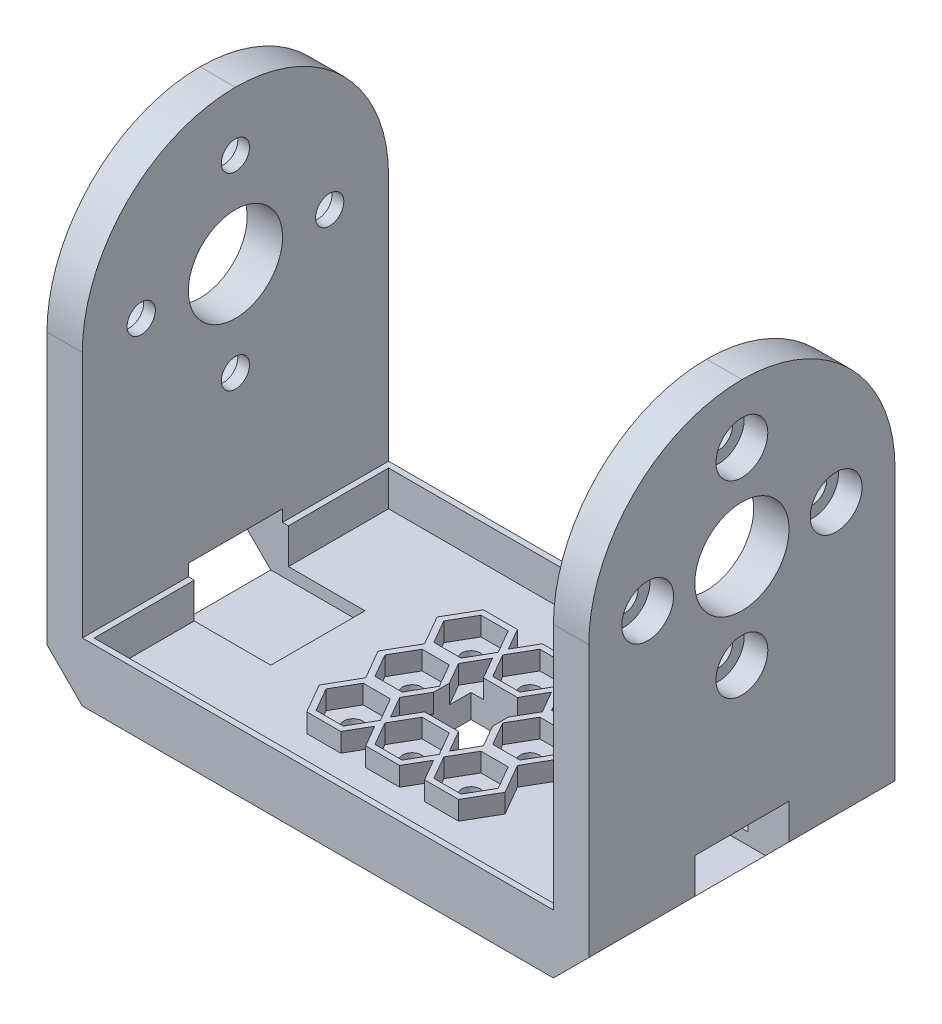
SolidWorks part; units mm, degrees
ref_plane "Front" through (0, 0, 0) normal (0, 0, 1) x (1, 0, 0)
ref_plane "Top" through (0, 0, 0) normal (0, 1, 0) x (1, 0, 0)
ref_plane "Right" through (0, 0, 0) normal (1, 0, 0) x (0, 0, -1)
sketch "草图1" plane through (0, 0, 0) normal (0, 1, 0) x (1, 0, 0)
  line L1 (-23, 13) -> (23, 13)
  line L2 (-23, 13) -> (-23, -13)
  line L3 (-23, -13) -> (23, -13)
  line L4 (23, 13) -> (23, -13)
  line L5 (-23, 13) -> (23, -13) construction
  line L6 (-23, -13) -> (23, 13) construction
  point P0 (0, 0)
  dimension "D1" = 46
  dimension "D2" = 26
extrude "凸台-拉伸1" add sketch "草图1" along normal blind 5
sketch "草图2" plane through (0, 5, 0) normal (0, 1, 0) x (1, 0, 0)
  line L0 (-23, -13) -> (23, -13) construction
  line L1 (-23, 13) -> (-20, 13)
  line L2 (-23, 13) -> (-23, -13)
  line L3 (-23, -13) -> (-20, -13)
  line L4 (-20, 13) -> (-20, -13)
  line L6 (23, 13) -> (20, 13)
  line L7 (23, 13) -> (23, -13)
  line L8 (23, -13) -> (20, -13)
  line L9 (20, 13) -> (20, -13)
  dimension "D1" = 3
  dimension "D2" = 3
extrude "凸台-拉伸2" add sketch "草图2" along normal blind 34
fillet "圆角1" radius 13 4 edges at (21.5, 39, -13) (-21.5, 39, -13) (21.5, 39, 13) (-21.5, 39, 13)
sketch "草图3" plane through (-23, 0, 0) normal (-1, 0, 0) x (0, 0, 1)
  line L0 (-13, 26) -> (13, 26) construction
  circle A0 centre (0, 26) radius 4
extrude "切除-拉伸1" cut sketch "草图3" against normal up to next
sketch "草图4" plane through (-23, 0, 0) normal (-1, 0, 0) x (0, 0, 1)
  line L0 (-13, 26) -> (13, 26) construction
  line L1 (0, 39) -> (0, 15.0372) construction
  point P9 (-8, 26)
  point P10 (0, 34)
  point P11 (8, 26)
  point P12 (0, 18)
  dimension "D1" = 8
  dimension "D2" = 8
  dimension "D3" = 8
  dimension "D4" = 8
hole_wizard "M2 凹头盖螺钉的柱形沉头孔1" positions "3D草图1" profile "草图5" counterbore size "M2" standard "ANSI Metric" end condition through all
sketch3d "3D草图1"
  point P0 (-23, 26, -8)
  point P3 (-23, 34, 0)
  point P6 (-23, 26, 8)
  point P9 (-23, 18, 0)
sketch "草图5" plane through (-23, 26, -8) normal (0, 1, 0) x (0, 0, 1)
  line L0 (0, 0) -> (0, 46)
  line L1 (0, 46) -> (1.2, 46)
  line L3 (1.2, 46) -> (1.2, 2)
  line L4 (1.2, 2) -> (2.2, 2)
  line L5 (2.2, 2) -> (2.2, 0)
  line L7 (2.2, 0) -> (0, 0)
  line L11 (0, -6.35) -> (0, 107.95) construction
  dimension "通孔孔直径" = 2.4
  dimension "通孔孔深度" = 46
  dimension "柱形沉头孔直径" = 4.4
  dimension "柱形沉头孔深度" = 2
mirror "镜向1" about plane through (0, 0, 0) normal (1, 0, 0) of "切除-拉伸1", "M2 凹头盖螺钉的柱形沉头孔1"
sketch "草图6" plane through (0, 5, 0) normal (0, 1, 0) x (1, 0, 0)
  line L8 (-19.5, -12.5) -> (19.5, -12.5)
  line L9 (19.5, -12.5) -> (19.5, 12.5)
  line L14 (19.5, 12.5) -> (-19.5, 12.5)
  line L15 (-19.5, 12.5) -> (-19.5, -12.5)
  line L16 (-19.5, -12.5) -> (19.5, -12.5)
  line L17 (19.5, -12.5) -> (19.5, 12.5)
  line L18 (19.5, 12.5) -> (-19.5, 12.5)
  line L19 (-19.5, 12.5) -> (-19.5, -12.5)
  dimension "D1" = 0.5
extrude "切除-拉伸3" cut sketch "草图6" against normal blind 3
chamfer "倒角1" distance 3 angle 45 2 edges at (23, 0, 0) (-23, 0, 0)
sketch "草图7" plane through (0, 2, 0) normal (0, 1, 0) x (1, 0, 0)
  line L0 (-19.5, 0) -> (-7.3094, 0) construction
  line L1 (-19.5, 12.5) -> (-19.5, -12.5) construction
  line L6 (-1.1547, 7) -> (-2.3094, 5)
  line L7 (-2.6906, 5) -> (-3.8453, 7)
  line L8 (-3.8453, 7) -> (-6.1547, 7)
  line L9 (-6.1547, 7) -> (-7.3094, 5)
  line L10 (-7.3094, 5) -> (-6.1547, 3)
  line L11 (-6.1547, 3) -> (-3.8453, 3)
  line L12 (-3.8453, 3) -> (-2.6906, 5)
  line L13 (1.1547, 7) -> (-1.1547, 7)
  line L14 (2.3094, 5) -> (1.1547, 7)
  line L15 (1.1547, 3) -> (2.3094, 5)
  line L16 (-1.1547, 3) -> (1.1547, 3)
  line L17 (-2.3094, 5) -> (-1.1547, 3)
  line L18 (3.8453, 7) -> (2.6906, 5)
  line L19 (6.1547, 7) -> (3.8453, 7)
  line L20 (7.3094, 5) -> (6.1547, 7)
  line L21 (6.1547, 3) -> (7.3094, 5)
  line L22 (3.8453, 3) -> (6.1547, 3)
  line L23 (2.6906, 5) -> (3.8453, 3)
  line L24 (-1.1547, 2) -> (-2.3094, 0)
  line L25 (1.1547, 2) -> (-1.1547, 2)
  line L26 (2.3094, 0) -> (1.1547, 2)
  line L27 (1.1547, -2) -> (2.3094, 0)
  line L28 (-1.1547, -2) -> (1.1547, -2)
  line L29 (-2.3094, 0) -> (-1.1547, -2)
  line L30 (3.8453, 2) -> (2.6906, 0)
  line L31 (6.1547, 2) -> (3.8453, 2)
  line L32 (6.1547, 2) -> (7.3094, 0)
  line L33 (7.3094, 0) -> (6.1547, -2)
  line L34 (3.8453, -2) -> (6.1547, -2)
  line L35 (2.6906, 0) -> (3.8453, -2)
  line L36 (-1.1547, -3) -> (-2.3094, -5)
  line L37 (1.1547, -3) -> (-1.1547, -3)
  line L38 (2.3094, -5) -> (1.1547, -3)
  line L39 (1.1547, -7) -> (2.3094, -5)
  line L40 (-1.1547, -7) -> (1.1547, -7)
  line L41 (-2.3094, -5) -> (-1.1547, -7)
  line L42 (3.8453, -3) -> (2.6906, -5)
  line L43 (6.1547, -3) -> (3.8453, -3)
  line L44 (7.3094, -5) -> (6.1547, -3)
  line L45 (6.1547, -7) -> (7.3094, -5)
  line L46 (3.8453, -7) -> (6.1547, -7)
  line L47 (2.6906, -5) -> (3.8453, -7)
  line L48 (-6.1547, 2) -> (-7.3094, 0)
  line L49 (-3.8453, 2) -> (-6.1547, 2)
  line L50 (-2.6906, 0) -> (-3.8453, 2)
  line L51 (-3.8453, -2) -> (-2.6906, 0)
  line L52 (-6.1547, -2) -> (-3.8453, -2)
  line L53 (-7.3094, 0) -> (-6.1547, -2)
  line L54 (-6.1547, -3) -> (-7.3094, -5)
  line L55 (-3.8453, -3) -> (-6.1547, -3)
  line L56 (-2.6906, -5) -> (-3.8453, -3)
  line L57 (-3.8453, -7) -> (-2.6906, -5)
  line L58 (-6.1547, -7) -> (-3.8453, -7)
  line L59 (-7.3094, -5) -> (-6.1547, -7)
  line L60 (-1.4434, 7.5) -> (-2.5, 5.6699)
  line L61 (-2.5, 4.3301) -> (-1.4434, 2.5)
  line L62 (-1.4434, 2.5) -> (1.4434, 2.5)
  line L63 (1.4434, 2.5) -> (2.5, 4.3301)
  line L64 (2.5, 5.6699) -> (1.4434, 7.5)
  line L65 (1.4434, 7.5) -> (-1.4434, 7.5)
  line L66 (-2.5, 5.6699) -> (-3.5566, 7.5)
  line L67 (-3.5566, 7.5) -> (-6.4434, 7.5)
  line L68 (-6.4434, 7.5) -> (-7.8868, 5)
  line L69 (-7.8868, 5) -> (-6.4434, 2.5)
  line L70 (-6.4434, 2.5) -> (-3.5566, 2.5)
  line L71 (-3.5566, 2.5) -> (-2.5, 4.3301)
  line L72 (3.5566, 7.5) -> (2.5, 5.6699)
  line L73 (2.5, 4.3301) -> (3.5566, 2.5)
  line L74 (3.5566, 2.5) -> (6.4434, 2.5)
  line L75 (6.4434, 2.5) -> (7.8868, 5)
  line L76 (7.8868, 5) -> (6.4434, 7.5)
  line L77 (6.4434, 7.5) -> (3.5566, 7.5)
  line L78 (-1.4434, 2.5) -> (-2.5, 0.6699)
  line L79 (-2.5, -0.6699) -> (-1.4434, -2.5)
  line L80 (-1.4434, -2.5) -> (1.4434, -2.5)
  line L81 (1.4434, -2.5) -> (2.5, -0.6699)
  line L82 (-1.4434, -2.5) -> (-2.8868, -5) construction
  line L83 (1.4434, 2.5) -> (-1.4434, 2.5)
  line L84 (3.5566, 2.5) -> (2.5, 0.6699)
  line L85 (2.5, -0.6699) -> (3.5566, -2.5)
  line L86 (3.5566, -2.5) -> (6.4434, -2.5)
  line L87 (6.4434, -2.5) -> (7.8868, 0)
  line L88 (7.8868, 0) -> (6.4434, 2.5)
  line L89 (6.4434, 2.5) -> (3.5566, 2.5)
  line L90 (-1.4434, -2.5) -> (-2.5, -4.3301)
  line L91 (-2.5, -5.6699) -> (-1.4434, -7.5)
  line L92 (-1.4434, -7.5) -> (1.4434, -7.5)
  line L93 (1.4434, -7.5) -> (2.5, -5.6699)
  line L95 (1.4434, -2.5) -> (-1.4434, -2.5)
  line L96 (3.5566, -2.5) -> (2.5, -4.3301)
  line L97 (2.5, -5.6699) -> (3.5566, -7.5)
  line L98 (3.5566, -7.5) -> (6.4434, -7.5)
  line L99 (6.4434, -7.5) -> (7.8868, -5)
  line L100 (7.8868, -5) -> (6.4434, -2.5)
  line L101 (6.4434, -2.5) -> (3.5566, -2.5)
  line L102 (-6.4434, 2.5) -> (-7.8868, 0)
  line L103 (-7.8868, 0) -> (-6.4434, -2.5)
  line L104 (-6.4434, -2.5) -> (-3.5566, -2.5)
  line L105 (-3.5566, -2.5) -> (-2.5, -0.6699)
  line L106 (-2.5, 0.6699) -> (-3.5566, 2.5)
  line L107 (-3.5566, 2.5) -> (-6.4434, 2.5)
  line L108 (-6.4434, -2.5) -> (-7.8868, -5)
  line L109 (-7.8868, -5) -> (-6.4434, -7.5)
  line L110 (-6.4434, -7.5) -> (-3.5566, -7.5)
  line L111 (-3.5566, -7.5) -> (-2.5, -5.6699)
  line L112 (2.1132, -5) -> (3.5566, -7.5) construction
  line L113 (-3.5566, -2.5) -> (-6.4434, -2.5)
  line L114 (-1.4434, 7.5) -> (-2.8868, 5) construction
  line L115 (-2.8868, 5) -> (-1.4434, 2.5) construction
  line L116 (-2.1132, 5) -> (-3.5566, 7.5) construction
  line L117 (-3.5566, 2.5) -> (-2.1132, 5) construction
  line L118 (2.1132, 5) -> (3.5566, 2.5) construction
  line L119 (3.5566, 7.5) -> (2.1132, 5) construction
  line L120 (2.8868, 5) -> (1.4434, 7.5) construction
  line L121 (1.4434, 2.5) -> (2.8868, 5) construction
  line L122 (-1.4434, 2.5) -> (-2.8868, 0) construction
  line L124 (-2.8868, 0) -> (-1.4434, -2.5) construction
  line L125 (-2.1132, 0) -> (-3.5566, 2.5) construction
  line L126 (-3.5566, -2.5) -> (-2.1132, 0) construction
  line L128 (2.1132, 0) -> (3.5566, -2.5) construction
  line L129 (3.5566, 2.5) -> (2.1132, 0) construction
  line L130 (2.5, 0.6699) -> (1.4434, 2.5)
  line L131 (2.8868, 0) -> (1.4434, 2.5) construction
  line L132 (-2.8868, -5) -> (-1.4434, -7.5) construction
  line L133 (1.4434, -2.5) -> (2.8868, 0) construction
  line L134 (3.5566, -2.5) -> (2.1132, -5) construction
  line L135 (-3.5566, -7.5) -> (-2.1132, -5) construction
  line L136 (-2.5, -4.3301) -> (-3.5566, -2.5)
  line L137 (-2.1132, -5) -> (-3.5566, -2.5) construction
  line L138 (2.5, -4.3301) -> (1.4434, -2.5)
  line L139 (2.8868, -5) -> (1.4434, -2.5) construction
  line L140 (1.4434, -7.5) -> (2.8868, -5) construction
  line L141 (6.1547, -2) -> (7.3094, 0) [skipped]
  line L142 (6.1547, -2) -> (7.3094, 0) construction
  line L143 (7.3094, 0) -> (6.1547, 2) [skipped]
  line L144 (7.3094, 0) -> (6.1547, 2) construction
  point P1 (-3.7209, 2)
  point P4 (-3.7209, 4.4996)
  dimension "D1" = 0.5
  dimension "D4" = 3
  dimension "D5" = 3
extrude "凸台-拉伸3" add sketch "草图7" along normal blind 1.6 contours L76 L77 L72 L64 L65 L60 L66 L67 L68 L69 L70 L71 L61 L62 L63 L73 L74 L75 L12 L11 L10 L9 L8 L7 L17 L6 L13 L14 L15 L16 L23 L18 L19 L20 L21 L22 | L84 L130 L62 L78 L106 L70 L102 L103 L104 L105 L79 L80 L81 L85 L86 L87 L88 L74 L29 L24 L25 L26 L27 L28 L35 L30 L31 L32 L33 L34 L53 L48 L49 L50 L51 L52 | L96 L138 L80 L90 L136 L104 L108 L109 L110 L111 L91 L92 L93 L97 L98 L99 L100 L86 L41 L36 L37 L38 L39 L40 L47 L42 L43 L44 L45 L46 L59 L54 L55 L56 L57 L58 region at (0, 2, -7.3345) region at (-5, 2, -2.3345) region at (-5, 2, 2.6655)
sketch "草图9" plane through (-23, 0, 0) normal (-1, 0, 0) x (0, 0, 1)
  line L4 (0, 5.6351) -> (0, -2.6444) construction
  line L5 (-12.5, 1) -> (12.5, 1)
  line L6 (-4, 1) -> (4, 1)
  line L7 (-4, 6) -> (4, 6)
  line L8 (-4, 6) -> (-4, 1)
  line L9 (4, 6) -> (4, 1)
  dimension "D2" = 4
  dimension "D1" = 1
extrude "切除-拉伸4" cut sketch "草图9" against normal blind 10
mirror "镜向2" about plane through (0, 0, 0) normal (1, 0, 0) of "切除-拉伸4"
sketch "草图10" plane through (0, 3.6, 0) normal (0, 1, 0) x (1, 0, 0)
  line L1 (-2.5, -2.5) -> (2.5, -2.5)
  line L2 (-2.5, -2.5) -> (-2.5, 2.5)
  line L3 (-2.5, 2.5) -> (2.5, 2.5)
  line L4 (2.5, -2.5) -> (2.5, 2.5)
  line L5 (-2.5, -2.5) -> (2.5, 2.5) construction
  line L6 (-2.5, 2.5) -> (2.5, -2.5) construction
  point P0 (0, 0)
  dimension "D1" = 5
  dimension "D2" = 5
extrude "切除-拉伸5" cut sketch "草图10" against normal blind 10
sketch "草图11" plane through (0, 2, 0) normal (0, 1, 0) x (1, 0, 0)
  point P0 (-5, 5)
  point P3 (0, 5)
  point P4 (5, 5)
  point P5 (0, 0)
  point P6 (5, 0)
  point P7 (0, -5)
  point P8 (5, -5)
  point P9 (-5, 0)
  point P10 (-5, -5)
  dimension "D1" = 3
  dimension "D2" = 3
hole_wizard "M2x0.4 螺纹孔1" positions "3D草图3" profile "草图13" tap size "M2x0.4" standard "ANSI Metric" end condition through all
sketch3d "3D草图3"
  point P0 (-5, 2, -5)
  point P3 (0, 2, -5)
  point P6 (5, 2, -5)
  point P9 (5, 2, 0)
  point P12 (-5, 2, 0)
  point P15 (-5, 2, 5)
  point P18 (0, 2, 5)
  point P21 (5, 2, 5)
sketch "草图13" plane through (-5, 2, -5) normal (1, 0, 0) x (0, 0, 1)
  line L0 (0, 0) -> (0, 2)
  line L1 (0, 2) -> (0.8, 2)
  line L2 (0.8, 2) -> (0.8, 0)
  line L5 (0.8, 0) -> (0, 0)
  line L11 (0, -6.35) -> (0, 107.95) construction
  dimension "通孔螺纹孔钻头直径" = 1.6
  dimension "通孔螺纹孔钻头深度" = 2
cosmetic thread "孔螺蚊线1" parameters "D2"=2
cosmetic thread "孔螺蚊线2" parameters "D2"=2
cosmetic thread "孔螺蚊线3" parameters "D2"=2
cosmetic thread "孔螺蚊线4" parameters "D2"=2
cosmetic thread "孔螺蚊线5" parameters "D2"=2
cosmetic thread "孔螺蚊线6" parameters "D2"=2
cosmetic thread "孔螺蚊线7" parameters "D2"=2
cosmetic thread "孔螺蚊线8" parameters "D2"=2
